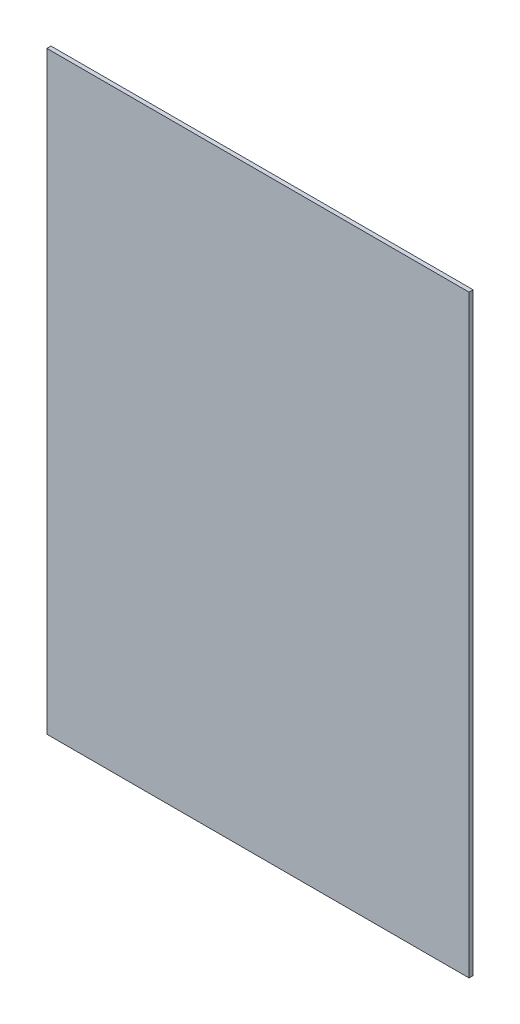
SolidWorks part; units mm, degrees
ref_plane "Спереди" through (0, 0, 0) normal (0, 0, 1) x (1, 0, 0)
ref_plane "Сверху" through (0, 0, 0) normal (0, 1, 0) x (1, 0, 0)
ref_plane "Справа" through (0, 0, 0) normal (1, 0, 0) x (0, 0, -1)
other "Configuration Table"
sketch "Эскиз1" plane through (0, 0, 0) normal (0, 0, 1) x (1, 0, 0)
  line L2 (-1138.3, -436.3) -> (-518, -436.3)
  line L3 (-1138.3, -436.3) -> (-1138.3, 436.3)
  line L4 (-1138.3, 436.3) -> (-518, 436.3)
  line L5 (-518, -436.3) -> (-518, 436.3)
extrude "Бобышка-Вытянуть1" add sketch "Эскиз1" against normal blind 6
equation "\"Глубина груза\"= 490"
equation "\"Высота груза\"= 297"
equation "\"Ширина ячейки\"= \"Ширина груза\" + 10"
equation "\"Глубина ячейки\"= \"Глубина груза\" + 10"
equation "\"Высота ячейки\"= \"Высота груза\" + 10 + 13"
equation "\"Колво ячеек ширина\"= 2"
equation "\"Колво ячеек высота\"= 2"
equation "\"Толщина стенки\" = 6"
equation "\"Крепление дверцы\"= 5"
equation "\"Ширина рейки\"= \"Толщина шестерни\""
equation "\"Высота рейки\"= 20"
equation "\"Высота пола\"= 20"
equation "\"Колво полозьев\"= 5"
equation "\"Отступ рейки\"= 20"
equation "\"Глубина каретки\"= \"Глубина ячейки\" + 30 + \"Мотор Y высота корпуса\" + 20"
equation "\"Длинна рейки\"= ( \"Ширина ячейки\" + \"Толщина стенки\" + \"Крепление дверцы\" ) * \"Колво ячеек ширина\" + \"Ширина ячейки выгрузки\" * \"Колво выгрузки\" + \"Толщина стенки\""
equation "\"Отступ шпильки\"= 26"
equation "\"Диаметр шпильки\"= 5"
equation "\"Длинна шпильки\"= ( \"Высота ячейки\" + \"Толщина стенки\" + \"Высота пола\" ) * \"Колво ячеек высота\" + ( \"Толщина стенки\" + \"Отступ рейки\" ) * 2 "
equation "\"Ширина пластины\"= 50  "
equation "\"Высота зона выгрузки\"= \"Высота ячейки\" * 2 + \"Толщина стенки\" * 2"
equation "\"Колво выгрузки\"= 1"
equation "\"Ширина ячейки выгрузки\"= \"Ширина ячейки\" + \"Толщина стенки\" + \"Отступ крепления мотора фиксации\"*2"
equation "\"Отступ крепления мотора фиксации\" = 30"
equation "\"Мотор X ширина корпуса\"= 42.3"
equation "\"Мотор X высота корпуса\"= 42.3"
equation "\"Мотор X длина корпуса\"= 40"
equation "\"Мотор X вылет вала\"= 19.8"
equation "\"Мотор Y ширина корпуса\"= 42.3"
equation "\"Мотор Y высота корпуса\"= 42.3"
equation "\"Мотор Y длина корпуса\"= 48"
equation "\"Мотор Y вылет вала\"= 30"
equation "\"Мотор Z ширина корпуса\"= 42"
equation "\"Мотор Z высота корпуса\"= 42"
equation "\"Мотор Z длина корпуса\"= 40"
equation "\"Мотор Z вылет вала\"= 23"
equation "\"Мотор диаметр вала ПРЕДВ\"= 5"
equation "\"Мотор шаг крепления ПРЕДВ\"= 31"
equation "\"Мотор диаметр отверстий ПРЕДВ\"= 3"
equation "\"Мотор глубина отверстий ПРЕДВ\"= 4.5"
equation "\"Мотор диаметр буртика ПРЕДВ\"= 22"
equation "\"Мотор высота буртика ПРЕДВ\"= 2"
equation "\"Мотор диаметр шкива ПРЕДВ\"= 16"
equation "\"Мотор длина шкива ПРЕДВ\"= 12"
equation "\"Мотор отступ шкива ПРЕДВ\"= 5"
equation "\"Мотор X шаг градусов\"= 1.8"
equation "\"Мотор Y шаг градусов\"= 1.8"
equation "\"Мотор Z шаг градусов\"= 1.8"
equation "\"Мотор Y диаметр ротора\"= 25.78"
equation "\"Толщина шестерни\"= 10"
equation "\"Ширина груза\"= 420"
equation "\"D1@Бобышка-Вытянуть1\"=\"Толщина стенки\""
